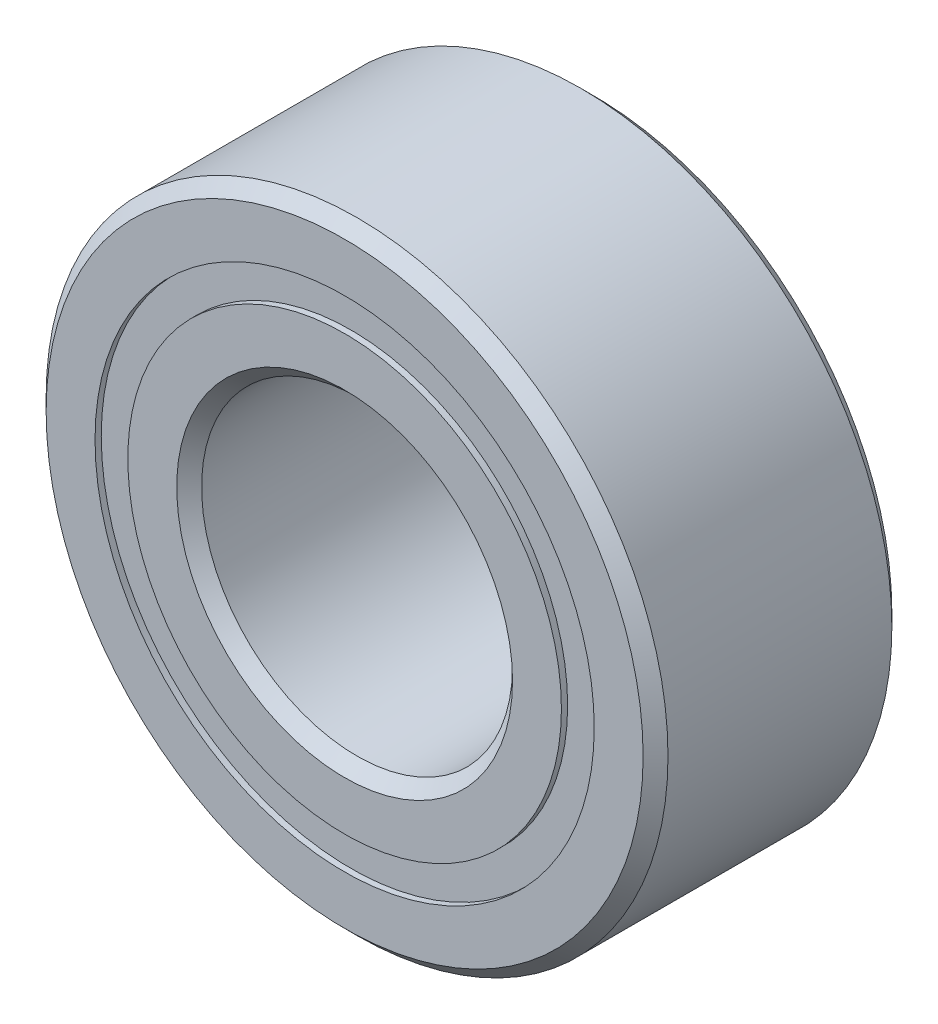
SolidWorks part; units mm, degrees
ref_plane "Front Plane" through (0, 0, 0) normal (0, 0, 1) x (1, 0, 0)
ref_plane "Top Plane" through (0, 0, 0) normal (0, 1, 0) x (1, 0, 0)
ref_plane "Right Plane" through (0, 0, 0) normal (1, 0, 0) x (0, 0, -1)
sketch "Sketch1" plane through (0, 0, 0) normal (1, 0, 0) x (0, 0, -1)
  line L0 (-2, 0) -> (2, 0) construction
  line L1 (0, 5) -> (0, -5) construction
  line L2 (1.8, 5) -> (-1.8, 5)
  line L3 (-1.8, 5) -> (-2, 4.8)
  line L4 (-2, 4.8) -> (-2, 4.0137)
  line L5 (-2, 4.0137) -> (-0.8889, 4.0137)
  line L6 (2, 4.0137) -> (0.8889, 4.0137)
  line L7 (2, 4.8) -> (2, 4.0137)
  line L8 (1.8, 5) -> (2, 4.8)
  line L9 (0, 5) -> (0, 3.75) construction
  line L10 (0, 3.75) -> (0, 2.5) construction
  arc A0 (-0.8889, 4.0137) -> (0.8889, 4.0137) centre (0, 3.75) cw
  point P14 (0, 2.5)
  dimension "D3" = 1.7778
  dimension "D1" = 45
  dimension "Width" = 4
  dimension "OD" = 10
  dimension "D2" = 0.2
  dimension "Shaft Dia" = 5
  dimension "D4" = 0.2637
revolve "Revolve1" add sketch "Sketch1" angle 360 about L0
sketch "Sketch3" plane through (0, 0, 0) normal (1, 0, 0) x (0, 0, -1)
  line L0 (-2, 3.4863) -> (-0.8889, 3.4863)
  line L1 (0, 5) -> (0, -5) construction
  line L2 (-2, 4.8) -> (-2, 4.0137) construction
  line L3 (-2, 3.4863) -> (-2, 2.7)
  line L4 (-1.8, 5) -> (-2, 4.8) construction
  line L5 (-2, 2.7) -> (-1.8, 2.5)
  line L6 (-1.8, 2.5) -> (1.8, 2.5)
  line L7 (1.8, 5) -> (1.8, -5) construction
  line L8 (1.8, 2.5) -> (2, 2.7)
  line L9 (2, -4.8) -> (2, 4.8) construction
  line L10 (2, 2.7) -> (2, 3.4863)
  line L11 (2, 3.4863) -> (0.8889, 3.4863)
  line L13 (1.8, 5) -> (2, 4.8) construction
  arc A0 (0.8889, 4.0137) -> (-0.8889, 4.0137) centre (0, 3.75) ccw construction
  arc A1 (0.8889, 3.4863) -> (-0.8889, 3.4863) centre (0, 3.75) cw
revolve "Revolve3" add sketch "Sketch3" angle 360 about L0
sketch "Sketch4" plane through (0, 0, 0) normal (1, 0, 0) x (0, 0, -1)
  line L0 (-0.9272, 3.75) -> (0.9272, 3.75)
  arc A2 (-0.9272, 3.75) -> (0.9272, 3.75) centre (0, 3.75) cw
  arc A3 (0.8889, 4.0137) -> (-0.8889, 4.0137) centre (0, 3.75) ccw construction
revolve "Revolve4" add sketch "Sketch4" angle 360 about L0
ref_axis "Axis1" through (0, 0, -2) along (0, 0, 1)
pattern_circular "CirPattern1" count 12 every 30 about axis through (0, 0, -2) along (0, 0, 1) of bodies 104
sketch "Sketch5" plane through (0, 0, 0) normal (1, 0, 0) x (0, 0, -1)
  line L0 (-2, 4.0137) -> (-0.8889, 4.0137) construction
  line L1 (-1.9, 4.0137) -> (-0.9272, 4.0137)
  line L2 (-1.9, 4.0137) -> (-1.9, 3.4863)
  line L3 (-1.9, 3.4863) -> (-0.9272, 3.4863)
  line L4 (-0.9272, 4.0137) -> (-0.9272, 3.4863)
  line L5 (-2, 3.4863) -> (-0.8889, 3.4863) construction
  line L6 (2, 4.0137) -> (0.8889, 4.0137) construction
  line L7 (1.9, 4.0137) -> (0.9272, 4.0137)
  line L8 (1.9, 4.0137) -> (1.9, 3.4863)
  line L9 (1.9, 3.4863) -> (0.9272, 3.4863)
  line L10 (0.9272, 4.0137) -> (0.9272, 3.4863)
  line L11 (2, 3.4863) -> (0.8889, 3.4863) construction
  line L12 (-1.8, 5) -> (-2, 4.8) construction
  point P18 (-1.9, 4.9)
revolve "Revolve5" add sketch "Sketch5" angle 360 about L0
sketch "Sketch6" plane through (0, 0, 0) normal (1, 0, 0) x (0, 0, -1)
  line L0 (2, 0) -> (-2, 0) construction
  line L1 (2, 4.0137) -> (1.2126, 4.0137)
  line L2 (2, 4.0137) -> (2, 6.9469)
  line L3 (2, 6.9469) -> (1.2126, 6.9469)
  line L4 (1.2126, 4.0137) -> (1.2126, 6.9469)
  dimension "Th" = 0.7874
  dimension "Flange OD" = 13.8938
revolve "Revolve6" [suppressed] add sketch "Sketch6" angle 360 about L0
equation "\"D2@Sketch1\" = \"Width@Sketch1\"*.05"
equation "\"D3@Sketch1\" = \"Width@Sketch1\"/2.25"
equation "\"D4@Sketch1\" = (((\"OD@Sketch1\"-\"Width@Sketch1\")/2)/3.25)/3.5"
equation "\"D2@CirPattern1\" = 360/\"Balls@CirPattern1\""
